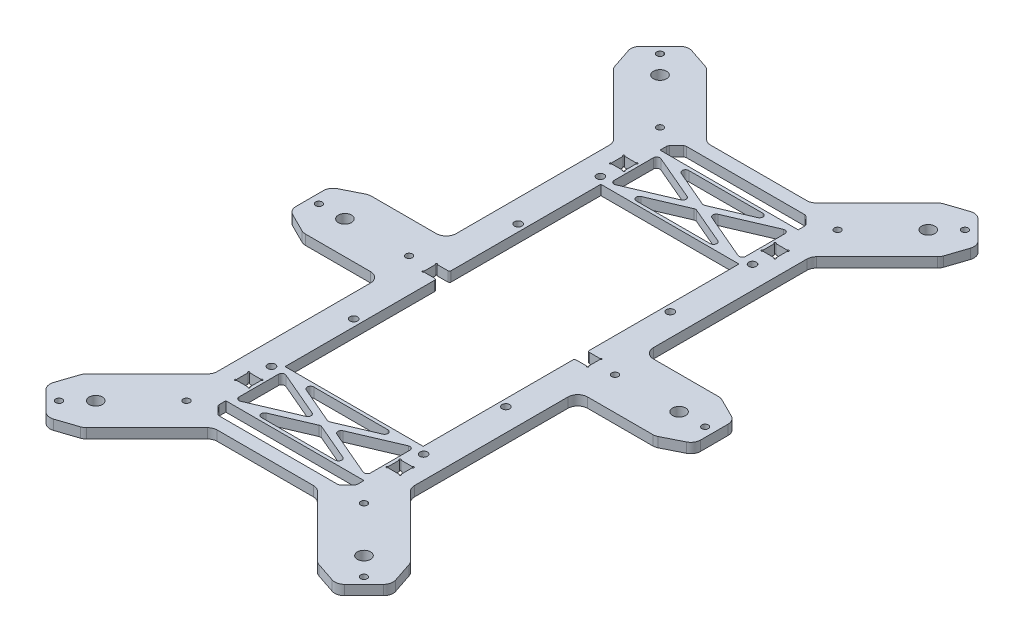
SolidWorks part; units mm, degrees
ref_plane "前视基准面" through (0, 0, 0) normal (0, 0, 1) x (1, 0, 0)
ref_plane "上视基准面" through (0, 0, 0) normal (0, 1, 0) x (1, 0, 0)
ref_plane "右视基准面" through (0, 0, 0) normal (1, 0, 0) x (0, 0, -1)
sketch "草图1" plane through (0, 0, 0) normal (0, 1, 0) x (1, 0, 0)
  line L0 (-30, 65) -> (-20, 75)
  line L1 (-20.5, 38) -> (20.5, 38) construction
  line L2 (-20.5, 38) -> (-20.5, -38) construction
  line L3 (-20.5, -38) -> (20.5, -38) construction
  line L4 (20.5, 38) -> (20.5, -38) construction
  line L5 (-20.5, 38) -> (20.5, -38) construction
  line L6 (-20.5, -38) -> (20.5, 38) construction
  line L7 (-20, 75) -> (20, 75)
  line L8 (-30, 65) -> (-30, -65)
  line L9 (-20, -75) -> (20, -75)
  line L10 (30, 65) -> (30, -65)
  line L11 (-30, 75) -> (30, -75) construction
  line L12 (-30, -75) -> (30, 75) construction
  line L13 (20, 75) -> (30, 65)
  line L14 (30, -65) -> (20, -75)
  line L15 (-30, -65) -> (-20, -75)
  line L16 (-1.6778, 71) -> (18.3431, 71)
  line L17 (18.3431, 71) -> (21, 68.3431)
  line L18 (21, 68.3431) -> (21, -68.3431)
  line L19 (0, 0) -> (21, 0) construction
  line L20 (0, 0) -> (0, 17.6719) construction
  line L21 (18.3431, -71) -> (21, -68.3431)
  line L22 (-1.6778, -71) -> (18.3431, -71)
  line L23 (1.6778, -71) -> (-18.3431, -71)
  line L24 (-18.3431, -71) -> (-21, -68.3431)
  line L25 (-21, 68.3431) -> (-21, -68.3431)
  line L26 (-18.3431, 71) -> (-21, 68.3431)
  line L27 (1.6778, 71) -> (-18.3431, 71)
  point P0 (0, 0)
  point P6 (0, 0)
  dimension "D1" = 41
  dimension "D2" = 76
  dimension "D3" = 60
  dimension "D4" = 150
  dimension "D5" = 9
  dimension "D6" = 4
  dimension "D11" = 4
extrude "凸台-拉伸1" add sketch "草图1" along normal mid plane 3 contours L8 L15 L9 L14 L10 L13 L7 L0 L27 L16 L17 L18 L21 L22 L23 L24 L25 L26 region at (-23.8576, 0, -68.8576)
sketch "草图2" plane through (0, 1.5, 0) normal (0, 1, 0) x (1, 0, 0)
  line L0 (0, 0) -> (45, 0) construction
  line L1 (33.5, 6) -> (56.5, 6) construction
  line L2 (33.5, 6) -> (33.5, -6) construction
  line L3 (33.5, -6) -> (56.5, -6) construction
  line L4 (56.5, 6) -> (56.5, -6) construction
  line L5 (33.5, 6) -> (56.5, -6) construction
  line L6 (33.5, -6) -> (56.5, 6) construction
  line L7 (25, 70) -> (46.3546, 91.3546) construction
  line L8 (28.5, 10) -> (60.5, 10)
  line L9 (28.5, 10) -> (28.5, -10)
  line L10 (28.5, -10) -> (60.5, -10)
  line L11 (61.5, 9) -> (61.5, -9)
  line L12 (28.5, 10) -> (61.5, -10) construction
  line L13 (28.5, -10) -> (61.5, 10) construction
  line L14 (20, 75) -> (30, 65) construction
  line L15 (24.2929, 77.7782) -> (32.7782, 69.2929) construction
  line L20 (24.2929, 77.7782) -> (40.5563, 94.0416) construction
  line L21 (32.7782, 69.2929) -> (49.0416, 85.5563) construction
  line L22 (40.5563, 94.0416) -> (49.0416, 85.5563) construction
  line L23 (44.799, 89.799) -> (28.5355, 73.5355) construction
  line L33 (54.6985, 85.5563) -> (30, 60.8579)
  line L34 (40.5563, 99.6985) -> (15.8579, 75)
  line L35 (41.9706, 99.6985) -> (54.6985, 86.9706)
  line L36 (20, 75) -> (30, 65)
  line L37 (45, 0) -> (58.7, 0) construction
  line L38 (45, 0) -> (45, 5.0576) construction
  line L39 (32.4246, 85.9099) -> (40.9099, 77.4246) construction
  line L40 (30, 65) -> (30, 60.8579)
  line L42 (20, 75) -> (15.8579, 75)
  arc A0 (60.5, -10) -> (61.5, -9) centre (60.5, -9) ccw
  arc A1 (60.5, 10) -> (61.5, 9) centre (60.5, 9) cw
  circle A4 centre (58.7, 0) radius 1
  circle A5 centre (31.3, 0) radius 1
  circle A6 centre (46.3546, 91.3546) radius 1
  circle A7 centre (26.9799, 71.9799) radius 1
  arc A8 (54.6985, 85.5563) -> (54.6985, 86.9706) centre (53.9914, 86.2635) ccw
  arc A9 (40.5563, 99.6985) -> (41.9706, 99.6985) centre (41.2635, 98.9914) cw
  point P0 (45, 0)
  dimension "D9" = 1
  dimension "D10" = 2
  dimension "D12" = 2
  dimension "D17" = 1
  dimension "D1" = 23
  dimension "D2" = 12
  dimension "D3" = 20
  dimension "D4" = 5
  dimension "D5" = 45
  dimension "D6" = 23
  dimension "D7" = 12
  dimension "D8" = 4
  dimension "D11" = 27.4
  dimension "D13" = 27.4
  dimension "D14" = 5
  dimension "D15" = 4
  dimension "D16" = 5
extrude "凸台-拉伸2" add sketch "草图2" against normal through all
mirror "镜向1" about plane through (0, 0, 0) normal (0, 0, 1) of "凸台-拉伸2"
mirror "镜向2" about plane through (0, 0, 0) normal (1, 0, 0) of "镜向1", "凸台-拉伸2"
sketch "草图3" plane through (0, 1.5, 0) normal (0, 1, 0) x (1, 0, 0)
  line L0 (21, 68.3431) -> (21, -68.3431) construction
  line L1 (21, 2) -> (25, 2)
  line L2 (21, 2) -> (21, -2)
  line L3 (21, -2) -> (25, -2)
  line L4 (25, 2) -> (25, -2)
  line L5 (21, 2) -> (25, -2) construction
  line L6 (21, -2) -> (25, 2) construction
  line L7 (0, 0) -> (23, 0) construction
  line L8 (21, -55) -> (25, -55)
  line L9 (21, 59) -> (25, 59)
  line L10 (21, 59) -> (21, 55)
  line L11 (21, 55) -> (25, 55)
  line L12 (25, 59) -> (25, 55)
  line L13 (21, 59) -> (25, 55) construction
  line L14 (21, 55) -> (25, 59) construction
  line L15 (25, -59) -> (25, -55)
  line L16 (21, -59) -> (25, -59)
  line L17 (21, -59) -> (21, -55)
  line L18 (0, 0) -> (0, 10.7772) construction
  line L19 (-21, 55) -> (-25, 55)
  line L20 (-25, 59) -> (-25, 55)
  line L21 (-21, 59) -> (-25, 59)
  line L22 (-21, 59) -> (-21, 55)
  line L23 (-21, -2) -> (-25, -2)
  line L24 (-25, 2) -> (-25, -2)
  line L25 (-21, 2) -> (-25, 2)
  line L26 (-21, 2) -> (-21, -2)
  line L27 (-21, -59) -> (-21, -55)
  line L28 (-21, -59) -> (-25, -59)
  line L29 (-25, -59) -> (-25, -55)
  line L30 (-21, -55) -> (-25, -55)
  point P0 (23, 0)
  point P10 (23, 57)
  dimension "D1" = 4
  dimension "D2" = 4
  dimension "D3" = 4
  dimension "D4" = 4
  dimension "D5" = 110
extrude "切除-拉伸1" cut sketch "草图3" against normal blind 3
sketch "草图4" plane through (0, 1.5, 0) normal (0, 1, 0) x (1, 0, 0)
  line L0 (0, 0) -> (0, 10.0171) construction
  circle A0 centre (25, 59) radius 0.25
  circle A1 centre (25, 55) radius 0.25
  circle A2 centre (25, 2) radius 0.25
  circle A3 centre (25, -2) radius 0.25
  circle A4 centre (25, -55) radius 0.25
  circle A5 centre (25, -59) radius 0.25
  circle A6 centre (-25, -59) radius 0.25
  circle A7 centre (-25, -55) radius 0.25
  circle A8 centre (-25, -2) radius 0.25
  circle A9 centre (-25, 2) radius 0.25
  circle A10 centre (-25, 55) radius 0.25
  circle A11 centre (-25, 59) radius 0.25
  dimension "D1" = 0.5
  dimension "D2" = 0.5
  dimension "D3" = 0.5
  dimension "D4" = 0.5
  dimension "D5" = 0.5
  dimension "D6" = 0.5
extrude "切除-拉伸2" cut sketch "草图4" against normal blind 3
fillet "圆角1" radius 0.5 4 edges at (21, 0, 2) (21, 0, -2) (-21, 0, 2) (-21, 0, -2)
fillet "圆角2" radius 1 8 edges at (21, 0, 68.3431) (18.3431, 0, 71) (-21, 0, 68.3431) (-18.3431, 0, 71) (21, 0, -68.3431) (18.3431, 0, -71) (-18.3431, 0, -71) (-21, 0, -68.3431)
fillet "圆角3" radius 3 6 edges at (-30, 0, 10) (30, 0, 10) (30, 0, 60.8579) (15.8579, 0, 75) (-15.8579, 0, 75) (-30, 0, 60.8579)
fillet "圆角4" radius 3 6 edges at (15.8579, 0, -75) (-15.8579, 0, -75) (-30, 0, -60.8579) (30, 0, -60.8579) (30, 0, -10) (-30, 0, -10)
sketch "草图5" plane through (0, -1.5, 0) normal (0, -1, 0) x (1, 0, 0)
  line L0 (-31.3, 0) -> (-50.8, 0) construction
  line L1 (-26.9799, -71.9799) -> (-40.7685, -85.7685) construction
  line L2 (-30.8787, -61.7365) -> (-54.6985, -85.5563) construction
  line L3 (0, 0) -> (-10.8594, 0) construction
  line L4 (0, 0) -> (0, -10.738) construction
  circle A0 centre (-50.8, 0) radius 2
  circle A1 centre (-31.3, 0) radius 1 construction
  circle A2 centre (-40.7685, -85.7685) radius 2
  circle A3 centre (-40.7685, 85.7685) radius 2
  circle A4 centre (40.7685, -85.7685) radius 2
  circle A5 centre (50.8, 0) radius 2
  circle A6 centre (40.7685, 85.7685) radius 2
  dimension "D1" = 4
  dimension "D4" = 4
  dimension "D2" = 19.5
  dimension "D3" = 19.5
extrude "切除-拉伸3" cut sketch "草图5" against normal blind 3
sketch "草图6" plane through (0, -1.5, 0) normal (0, -1, 0) x (1, 0, 0)
  line L0 (0, 0) -> (0, -18.353) construction
  circle A0 centre (-50.8, 0) radius 4
  circle A1 centre (-40.7685, 85.7685) radius 4
  circle A2 centre (-40.7685, -85.7685) radius 4
  circle A3 centre (40.7685, -85.7685) radius 4
  circle A4 centre (40.7685, 85.7685) radius 4
  circle A5 centre (50.8, 0) radius 4
  dimension "D1" = 8
  dimension "D2" = 8
  dimension "D3" = 8
extrude "切除-拉伸4" [suppressed] cut sketch "草图6" against normal blind 2
sketch "草图7" plane through (0, -1.5, 0) normal (0, -1, 0) x (1, 0, 0)
  line L0 (-23.125, -25) -> (-23.125, -2) construction
  line L1 (-21.5, -2) -> (-24.75, -2) construction
  line L2 (-23.125, -25) -> (-23.125, -50) construction
  line L3 (0, 0) -> (-7.295, 0) construction
  line L4 (0, 0) -> (0, -14.9921) construction
  circle A0 centre (-23.125, -25) radius 1.15
  circle A1 centre (-23.125, -50) radius 1.15
  circle A2 centre (-23.125, 50) radius 1.15
  circle A3 centre (-23.125, 25) radius 1.15
  circle A4 centre (23.125, -25) radius 1.15
  circle A5 centre (23.125, -50) radius 1.15
  circle A6 centre (23.125, 25) radius 1.15
  circle A7 centre (23.125, 50) radius 1.15
  dimension "D1" = 2.3
  dimension "D2" = 2.3
  dimension "D3" = 25
  dimension "D4" = 25
extrude "切除-拉伸5" cut sketch "草图7" against normal through all
sketch "草图8" plane through (0, 1.5, 0) normal (0, 1, 0) x (1, 0, 0)
  line L0 (61.5, 6) -> (53.5, 10)
  line L1 (61.5, -9) -> (61.5, 9) construction
  line L2 (60.5, 10) -> (33, 10) construction
  line L3 (0, 0) -> (28.1061, 0) construction
  line L4 (61.5, -6) -> (53.5, -10)
  line L5 (33, -10) -> (60.5, -10) construction
  line L6 (53.5, -10) -> (60.5, -10)
  line L7 (60.5, 10) -> (53.5, 10)
  line L8 (61.5, -9) -> (61.5, -6)
  line L9 (61.5, 6) -> (61.5, 9)
  line L10 (26.9799, -71.9799) -> (40.7685, -85.7685) construction
  line L11 (52.5772, -89.0919) -> (49.7487, -80.6066)
  line L12 (54.6985, -86.9706) -> (41.9706, -99.6985) construction
  line L13 (30.8787, -61.7365) -> (54.6985, -85.5563) construction
  line L14 (44.0919, -97.5772) -> (35.6066, -94.7487)
  line L15 (54.6985, -86.9706) -> (52.5772, -89.0919)
  line L16 (44.0919, -97.5772) -> (41.9706, -99.6985)
  line L17 (49.7487, -80.6066) -> (54.6985, -85.5563)
  line L18 (40.5563, -99.6985) -> (16.7365, -75.8787) construction
  line L19 (40.5563, -99.6985) -> (35.6066, -94.7487)
  line L20 (52.5772, 89.0919) -> (49.7487, 80.6066)
  line L21 (54.6985, 86.9706) -> (52.5772, 89.0919)
  line L22 (49.7487, 80.6066) -> (54.6985, 85.5563)
  line L23 (44.0919, 97.5772) -> (41.9706, 99.6985)
  line L24 (44.0919, 97.5772) -> (35.6066, 94.7487)
  line L25 (40.5563, 99.6985) -> (35.6066, 94.7487)
  line L26 (0, 0) -> (0, 26.4236) construction
  line L27 (-44.0919, -97.5772) -> (-41.9706, -99.6985)
  line L28 (-44.0919, -97.5772) -> (-35.6066, -94.7487)
  line L29 (-40.5563, -99.6985) -> (-35.6066, -94.7487)
  line L30 (-52.5772, -89.0919) -> (-49.7487, -80.6066)
  line L31 (-54.6985, -86.9706) -> (-52.5772, -89.0919)
  line L32 (-49.7487, -80.6066) -> (-54.6985, -85.5563)
  line L33 (-53.5, -10) -> (-60.5, -10)
  line L34 (-61.5, -6) -> (-53.5, -10)
  line L35 (-61.5, -9) -> (-61.5, -6)
  line L36 (-61.5, 6) -> (-61.5, 9)
  line L37 (-61.5, 6) -> (-53.5, 10)
  line L38 (-60.5, 10) -> (-53.5, 10)
  line L39 (-54.6985, 86.9706) -> (-52.5772, 89.0919)
  line L40 (-52.5772, 89.0919) -> (-49.7487, 80.6066)
  line L41 (-49.7487, 80.6066) -> (-54.6985, 85.5563)
  line L42 (-40.5563, 99.6985) -> (-35.6066, 94.7487)
  line L43 (-44.0919, 97.5772) -> (-35.6066, 94.7487)
  line L44 (-44.0919, 97.5772) -> (-41.9706, 99.6985)
  arc A0 (60.5, -10) -> (61.5, -9) centre (60.5, -9) ccw construction
  arc A1 (61.5, 9) -> (60.5, 10) centre (60.5, 9) ccw construction
  arc A2 (60.5, -10) -> (61.5, -9) centre (60.5, -9) ccw
  arc A3 (61.5, 9) -> (60.5, 10) centre (60.5, 9) ccw
  arc A4 (54.6985, -86.9706) -> (54.6985, -85.5563) centre (53.9914, -86.2635) ccw construction
  arc A5 (54.6985, -86.9706) -> (54.6985, -85.5563) centre (53.9914, -86.2635) ccw
  arc A6 (40.5563, -99.6985) -> (41.9706, -99.6985) centre (41.2635, -98.9914) ccw construction
  arc A7 (40.5563, -99.6985) -> (41.9706, -99.6985) centre (41.2635, -98.9914) ccw
  arc A8 (54.6985, 86.9706) -> (54.6985, 85.5563) centre (53.9914, 86.2635) cw
  arc A9 (40.5563, 99.6985) -> (41.9706, 99.6985) centre (41.2635, 98.9914) cw
  arc A10 (-40.5563, -99.6985) -> (-41.9706, -99.6985) centre (-41.2635, -98.9914) cw
  arc A11 (-54.6985, -86.9706) -> (-54.6985, -85.5563) centre (-53.9914, -86.2635) cw
  arc A12 (-60.5, -10) -> (-61.5, -9) centre (-60.5, -9) cw
  arc A13 (-61.5, 9) -> (-60.5, 10) centre (-60.5, 9) cw
  arc A14 (-54.6985, 86.9706) -> (-54.6985, 85.5563) centre (-53.9914, 86.2635) ccw
  arc A15 (-40.5563, 99.6985) -> (-41.9706, 99.6985) centre (-41.2635, 98.9914) ccw
  dimension "D1" = 4
  dimension "D2" = 8
  dimension "D3" = 4
  dimension "D4" = 8
extrude "切除-拉伸6" cut sketch "草图8" against normal up to next
fillet "圆角5" radius 3 24 edges at (-35.6066, 0, -94.7487) (-44.0919, 0, -97.5772) (-52.5772, 0, -89.0919) (-49.7487, 0, -80.6066) (-53.5, 0, -10) (-53.5, 0, 10) (-61.5, 0, 6) (-61.5, 0, -6) (-49.7487, 0, 80.6066) (-35.6066, 0, 94.7487) (-52.5772, 0, 89.0919) (-44.0919, 0, 97.5772) (35.6066, 0, 94.7487) (44.0919, 0, 97.5772) (49.7487, 0, 80.6066) (52.5772, 0, 89.0919) (49.7487, 0, -80.6066) (52.5772, 0, -89.0919) (35.6066, 0, -94.7487) (44.0919, 0, -97.5772) (53.5, 0, 10) (61.5, 0, 6) (53.5, 0, -10) (61.5, 0, -6)
sketch "草图9" plane through (0, 1.5, 0) normal (0, 1, 0) x (1, 0, 0)
  line L0 (21, 55) -> (21, 2.5) construction
  line L1 (-21, 66) -> (21, 66)
  line L2 (-21, 66) -> (-21, 48)
  line L3 (-21, 48) -> (21, 48)
  line L4 (21, 66) -> (21, 48)
  line L5 (-21, 66) -> (21, 48) construction
  line L6 (-21, 48) -> (21, 66) construction
  line L7 (0, 0) -> (0, 57) construction
  line L8 (0, 0) -> (16.4102, 0) construction
  line L9 (-21, -48) -> (21, -48)
  line L10 (21, -66) -> (21, -48)
  line L11 (-21, -66) -> (21, -66)
  line L12 (-21, -66) -> (-21, -48)
  point P0 (0, 57)
  dimension "D1" = 18
  dimension "D2" = 57
extrude "凸台-拉伸3" add sketch "草图9" against normal blind 3
sketch "草图10" plane through (0, 1.5, 0) normal (0, 1, 0) x (1, 0, 0)
  line L0 (21, 66) -> (-21, 48) construction
  line L1 (21, 48) -> (-21, 66) construction
  line L3 (16.1281, 65) -> (0, 58.088)
  line L4 (20, 64.4835) -> (2.5386, 57)
  line L5 (0, 55.912) -> (-16.1281, 49)
  line L6 (16.1281, 49) -> (0, 55.912)
  line L9 (20, 49.5165) -> (2.5386, 57)
  line L10 (0, 58.088) -> (-16.1281, 65)
  line L11 (-2.5386, 57) -> (-20, 49.5165)
  line L12 (-21, 49) -> (21, 49)
  line L13 (-16.1281, 49) -> (16.1281, 49)
  line L14 (20, 64.4835) -> (20, 49.5165)
  line L15 (21.3939, 65.0809) -> (-20.6061, 47.0809) construction
  line L16 (-2.5386, 57) -> (-20, 64.4835)
  line L17 (20.6061, 66.9191) -> (-21.3939, 48.9191) construction
  line L18 (16.1281, 65) -> (-16.1281, 65)
  line L19 (0, 0) -> (16.1281, 0) construction
  line L20 (0, -55.912) -> (-16.1281, -49)
  line L21 (-20, 64.4835) -> (-20, 49.5165)
  line L22 (16.1281, -49) -> (0, -55.912)
  line L24 (20.6061, 47.0809) -> (-21.3939, 65.0809) construction
  line L25 (-16.1281, -49) -> (16.1281, -49)
  line L26 (-2.5386, -57) -> (-20, -49.5165)
  line L27 (-20, -64.4835) -> (-20, -49.5165)
  line L28 (-2.5386, -57) -> (-20, -64.4835)
  line L29 (16.1281, -65) -> (0, -58.088)
  line L30 (16.1281, -65) -> (-16.1281, -65)
  line L31 (0, -58.088) -> (-16.1281, -65)
  line L32 (20, -64.4835) -> (20, -49.5165)
  line L33 (20, -49.5165) -> (2.5386, -57)
  line L34 (20, -64.4835) -> (2.5386, -57)
  dimension "D1" = 1
  dimension "D2" = 1
  dimension "D4" = 1
  dimension "D6" = 1
extrude "切除-拉伸7" cut sketch "草图10" against normal blind 3
fillet "圆角6" radius 1 24 edges at (-16.1281, 0, 49) (16.1281, 0, 49) (0, 0, 55.912) (-20, 0, 49.5165) (-2.5386, 0, 57) (-20, 0, 64.4835) (0, 0, 58.088) (-16.1281, 0, 65) (16.1281, 0, 65) (20, 0, 64.4835) (2.5386, 0, 57) (20, 0, 49.5165) (0, 0, -55.912) (-16.1281, 0, -49) (16.1281, 0, -49) (-16.1281, 0, -65) (16.1281, 0, -65) (0, 0, -58.088) (-2.5386, 0, -57) (-20, 0, -49.5165) (-20, 0, -64.4835) (20, 0, -49.5165) (2.5386, 0, -57) (20, 0, -64.4835)
sketch "草图11" plane through (0, 1.5, 0) normal (0, 1, 0) x (1, 0, 0)
  line L0 (0, 0) -> (0, -14.3193) construction
  line L1 (0, 0) -> (13.0818, 0) construction
  circle A0 centre (21, -55) radius 0.25
  circle A1 centre (21, -59) radius 0.25
  circle A2 centre (-21, -59) radius 0.25
  circle A3 centre (-21, -55) radius 0.25
  circle A4 centre (-21, 55) radius 0.25
  circle A5 centre (-21, 59) radius 0.25
  circle A6 centre (21, 59) radius 0.25
  circle A7 centre (21, 55) radius 0.25
  dimension "D1" = 0.5
  dimension "D2" = 0.5
extrude "切除-拉伸8" cut sketch "草图11" against normal blind 3
